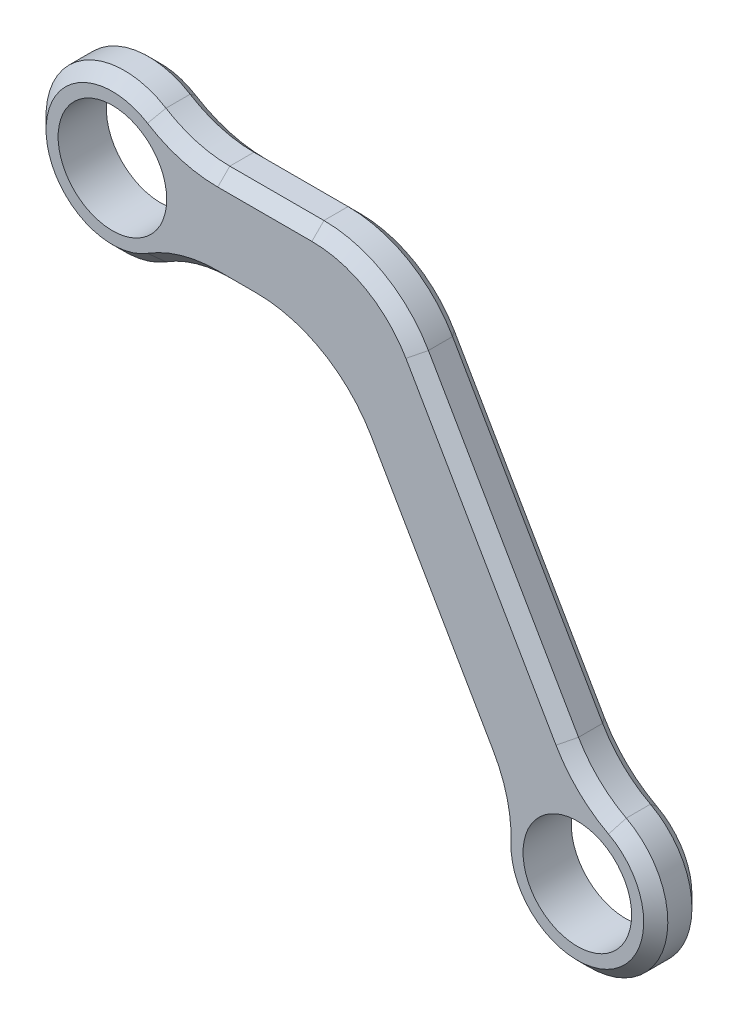
SolidWorks part; units mm, degrees
ref_plane "Front Plane" through (0, 0, 0) normal (0, 0, 1) x (1, 0, 0)
ref_plane "Top Plane" through (0, 0, 0) normal (0, 1, 0) x (1, 0, 0)
ref_plane "Right Plane" through (0, 0, 0) normal (1, 0, 0) x (0, 0, -1)
sketch "Sketch1" plane through (0, 0, 0) normal (0, 0, 1) x (1, 0, 0)
  line L0 (0, 0) -> (20, 0) construction
  line L1 (20, 0) -> (38.5373, -32.1076) construction
  line L2 (5.1235, -4) -> (17.6906, -4)
  line L3 (17.6906, -4) -> (32.5115, -29.6706)
  line L4 (5.1235, 4) -> (22.3094, 4)
  line L5 (22.3094, 4) -> (39.4397, -25.6706)
  line L6 (0, 4) -> (22.3094, 4) construction
  line L7 (0, -4) -> (17.6906, -4) construction
  line L8 (0, 0) -> (38.5373, -32.1076) construction
  line L9 (22.3094, 4) -> (42.0014, -30.1076) construction
  line L10 (17.6906, -4) -> (35.0732, -34.1076) construction
  circle A0 centre (0, 0) radius 4.5
  arc A1 (5.1235, 4) -> (5.1235, -4) centre (0, 0) ccw
  arc A2 (32.5115, -29.6706) -> (39.4397, -25.6706) centre (38.5373, -32.1076) ccw
  circle A3 centre (38.5373, -32.1076) radius 4.5
  dimension "D1" = 9
  dimension "D2" = 13
  dimension "D6" = 9
  dimension "D7" = 13
  dimension "D3" = 20
  dimension "D4" = 50.16
  dimension "D5" = 60
  dimension "D8" = 4
  dimension "D9" = 4
extrude "Boss-Extrude1" add sketch "Sketch1" along normal blind 4
fillet "Fillet1" radius 10 6 edges at (17.6906, -4, 2) (22.3094, 4, 2) (32.5115, -29.6706, 2) (39.4397, -25.6706, 2) (5.1235, -4, 2) (5.1235, 4, 2)
chamfer "Chamfer2" distance 1 angle 45 24 edges at (39.3461, -24.7359, 4) (41.7873, -37.7368, 4) (31.7489, -29.1222, 4) (25.6423, -17.7727, 4) (16.9171, -5.3397, 4) (10.3246, -4, 4) (5.9797, -4.3862, 4) (-6.5, 0, 4) (5.9797, 4.3862, 4) (12.634, 4, 4) (21.5359, 2.6603, 4) (31.4158, -11.7727, 4) (16.9171, -5.3397, 0) (10.3246, -4, 0) (25.6423, -17.7727, 0) (5.9797, -4.3862, 0) (31.7489, -29.1222, 0) (-6.5, 0, 0) (41.7873, -37.7368, 0) (5.9797, 4.3862, 0) (39.3461, -24.7359, 0) (12.634, 4, 0) (31.4158, -11.7727, 0) (21.5359, 2.6603, 0)
